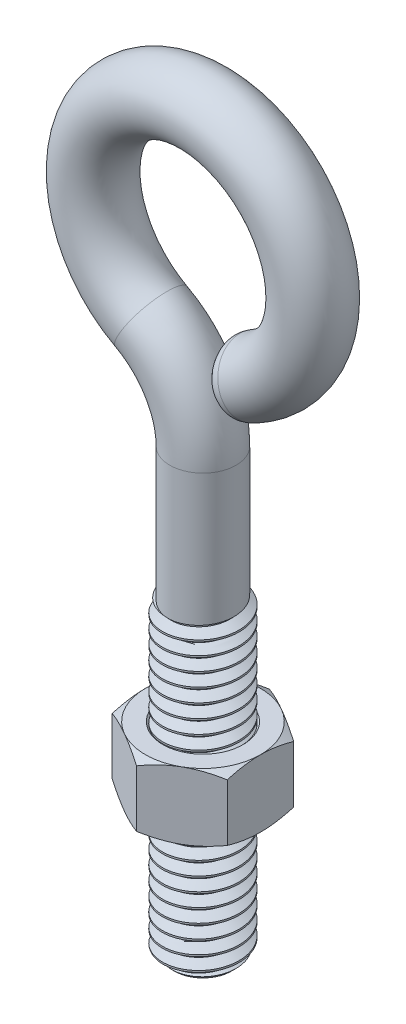
SolidWorks part; units mm, degrees
note: '?' marks a value the reader was unsure of.
ref_plane "Front Plane" through (0, 0, 0) normal (0, 0, 1) x (1, 0, 0)
ref_plane "Top Plane" through (0, 0, 0) normal (0, 1, 0) x (1, 0, 0)
ref_plane "Right Plane" through (0, 0, 0) normal (1, 0, 0) x (0, 0, -1)
sketch "Sketch1" plane through (0, 0, 0) normal (0, 0, 1) x (1, 0, 0)
  line L0 (0, -13.7795) -> (0, -64.5795) construction
  line L1 (-3.9687, -64.5795) -> (3.9688, -64.5795) construction
  line L2 (0, -32.8295) -> (3.9688, -32.8295) construction
  line L3 (0, -13.7795) -> (0, -7.9375) construction
  line L4 (-3.429, -32.8295) -> (3.429, -32.8295) construction
  line L5 (3.429, -32.8295) -> (3.429, -13.7795) construction
  line L6 (-3.9687, -64.5795) -> (-3.9687, -63.1684) construction
  line L7 (3.9688, -64.5795) -> (3.9688, -32.8295) construction
  line L8 (3.429, -13.7795) -> (0, -13.7795) construction
  circle A0 centre (0, 0) radius 14.7955 construction
  circle A1 centre (0, 11.3665) radius 3.429 construction
  circle A2 centre (0, 0) radius 7.9375 construction
  point P9 (0, -13.7795)
  point P10 (0, 14.7955)
  point P11 (0, 7.9375)
  point P14 (0, -64.5795)
  point P22 (0, -14.7955)
  point P24 (0, -32.8295)
  point P27 (-3.9687, -64.5795)
  point P28 (3.9688, -64.5795)
  point P30 (-3.429, -32.8295)
  point P31 (-3.429, -36.3573)
  dimension "Pitch" = 1.4111
  dimension "A" = 6.858
  dimension "Eye Dia." = 15.875
  dimension "Shank Lg." = 50.8
  dimension "Thread OD" = 7.9375
  dimension "Thread Lg." = 31.75
  dimension "Overall Lg." = 79.375
  dimension "Wire OD." = 6.858
  dimension "OD" = 29.591
  dimension "D1" = 3.5278
sketch "Sketch2" plane through (0, 0, 0) normal (0, 1, 0) x (1, 0, 0)
  circle A0 centre (0, 0) radius 3.9688
extrude "Boss-Extrude1" add sketch "Sketch2" against normal up to vertex (64.5795 mm away) from vertex at -32.8295 starting at point (0, -32.8295, 0)
sketch "Sketch3" plane through (0, -64.5795, 0) normal (0, -1, 0) x (1, 0, 0)
  circle A1 centre (0, 0) radius 3.9688
  circle A2 centre (0, 0) radius 3.9688
  point P0 (3.9688, 0)
  point P1 (0, -3.9688)
  dimension "D1" = 0
sketch "Sketch7" plane through (0, -32.8295, 0) normal (0, 1, 0) x (1, 0, 0)
  circle A0 centre (0, 0) radius 3.429
sketch "Sketch8" plane through (0, 0, 0) normal (0, 0, 1) x (1, 0, 0)
  line L1 (0, -18.978) -> (0, -32.8295)
  line L2 (0, -13.7795) -> (0, -7.9375) construction
  line L3 (0, -13.7795) -> (0, -64.5795) construction
  line L4 (-10.16, -18.978) -> (-1.4438, -13.7576) construction
  arc A0 (3.3898, -10.8493) -> (-5.3647, -10.0208) centre (0, 0) ccw
  arc A1 (-5.3647, -10.0208) -> (0, -18.978) centre (-10.16, -18.978) cw
  circle A3 centre (0, -11.3665) radius 3.429 construction
  dimension "D1" = 10.16
sweep "Sweep1" add profiles "Sketch7" path "Sketch8"
fillet "Fillet1" radius 1.9844 1 edges at (3.3898, -10.8493, 3.429)
chamfer "Chamfer1" distance 1.0319 angle 45 1 edges at (0, -64.5795, 3.9688)
sketch "Sketch9" plane through (0, -64.5795, 0) normal (0, -1, 0) x (1, 0, 0)
  line L1 (0, 6.8741) -> (-5.9531, 3.437)
  line L2 (-5.9531, 3.437) -> (-5.9531, -3.437)
  line L3 (-5.9531, -3.437) -> (0, -6.8741)
  line L4 (0, -6.8741) -> (5.9531, -3.437)
  line L5 (5.9531, -3.437) -> (5.9531, 3.437)
  line L6 (5.9531, 3.437) -> (0, 6.8741)
  circle A0 centre (0, 0) radius 5.9531 construction
  circle A1 centre (0, 0) radius 3.9688
extrude "Boss-Extrude2" add sketch "Sketch9" against normal blind 6.9453 from offset 13.97 separate body offset against normal yes
sketch "Sketch10" plane through (0, 0, 0) normal (1, 0, 0) x (0, 0, -1)
  line L0 (-5.9531, -43.6642) -> (-7.795, -43.6642)
  line L1 (-7.795, -43.6642) -> (-7.795, -50.6095)
  line L2 (-7.795, -50.6095) -> (-5.9531, -50.6095)
  line L3 (-5.9531, -50.6095) -> (-6.8741, -50.0778)
  line L4 (-6.8741, -50.0778) -> (-6.8741, -44.1959)
  line L5 (-6.8741, -44.1959) -> (-5.9531, -43.6642)
  line L6 (-3.7924, -43.6642) -> (-3.7924, -50.6095)
  line L7 (-3.7924, -50.6095) -> (-4.1451, -50.6095)
  line L8 (-4.1451, -50.6095) -> (-3.9688, -50.4331)
  line L9 (-3.9688, -50.4331) -> (-3.9688, -43.8406)
  line L10 (-3.9688, -43.8406) -> (-4.1451, -43.6642)
  line L11 (-4.1451, -43.6642) -> (-3.7924, -43.6642)
  line L12 (-3.9688, -43.6642) -> (-3.9688, -50.6095) construction
  line L14 (-3.9688, -50.4331) -> (-3.9688, -50.6095) construction
  line L15 (-3.9688, -43.8406) -> (-3.9688, -43.6642) construction
  line L16 (-6.8741, -43.6642) -> (-6.8741, -50.6095) construction
  line L18 (-5.9531, -50.6095) -> (-5.9531, -64.5795) construction
  dimension "D1" = 60
  dimension "D2" = 45
  dimension "D3" = 0.1764
revolve "Cut-Revolve1" cut sketch "Sketch10" angle 360 about L0
ref_axis "Center Axis 1" through (0, -13.7795, 0) along (0, -1, 0)?
curve "Helix/Spiral1" pitch 1.4111 height 33.1611 turns 23.5 parameters "Pitch"=1.4111
sketch "Sketch4" plane through (0, 0, 0) normal (0, 0, 1) x (1, 0, 0)
  line L0 (4.1215, -64.4913) -> (4.1215, -65.9024) construction
  line L1 (4.1215, -65.9024) -> (2.8994, -65.1969) construction
  line L2 (2.8994, -65.1969) -> (4.1215, -64.4913) construction
  line L3 (3.0522, -65.1087) -> (3.0522, -65.2851) construction
  line L4 (3.9688, -64.5795) -> (3.9688, -65.8142) construction
  line L5 (2.8994, -65.1969) -> (3.0522, -65.1969) construction
  line L6 (3.9688, -65.1969) -> (4.1215, -65.1969) construction
  line L7 (4.0451, -64.5354) -> (3.0522, -65.1087)
  line L8 (3.0522, -65.1087) -> (3.0522, -65.2851)
  line L9 (3.0522, -65.2851) -> (4.0451, -65.8583)
  line L10 (4.0451, -65.8583) -> (4.0451, -64.5354)
  point P13 (4.0451, -65.1969)
  dimension "D1" = 1.4111
  dimension "D2" = 0.1764
sweep "Cut-Sweep1" cut profiles "Sketch4" path "Helix/Spiral1"
sketch "SketchX" plane through (0, 0, 0) normal (1, 0, 0) x (0, 0, -1)
  line L0 (3.9688, -64.5795) -> (3.9688, -38.1212) construction
  dimension "D1" = 26.4583
equation "\"D3@Helix/Spiral1\" = \"Pitch@Helix/Spiral1\" + \"Thread Lg.@Sketch1\""
equation "\"D1@Sketch4\" = \"Pitch@Helix/Spiral1\""
equation "\"A@Sketch1\" = \"Wire OD.@Sketch1\""
equation "\"D2@Sketch4\" = \"D1@Sketch4\" / 8"
equation "\"D1@Fillet1\" = \"Thread OD@Sketch1\" / 4"
equation "\"D1@SketchX\" = \"Thread Lg.@Sketch1\" -  ( \"Pitch@Helix/Spiral1\" *  4 ) +  ( \"Pitch@Helix/Spiral1\" /  4 ) "
equation "\"Nut Wd.@Sketch9\" = \"Thread OD@Sketch1\" * 1.5"
equation "\"Nut Ht.@Boss-Extrude2\" = \"Thread OD@Sketch1\" * 0.875"
equation "\"Offset@Boss-Extrude2\"=\"Thread Lg.@Sketch1\"*.44"
equation "\"D3@Sketch10\" = \"Pitch@Helix/Spiral1\" / 8"
equation "\"D1@Chamfer1\"=\"Thread OD@Sketch1\"*.13"
equation "\"D1@Sketch8\"=\"Shank Lg.@Sketch1\"*.2"
equation "\"Pitch@Helix/Spiral1\"=\"Pitch@Sketch1\""
equation "\"D1@Sketch1\"=\"Pitch@Sketch1\"*2.5"
